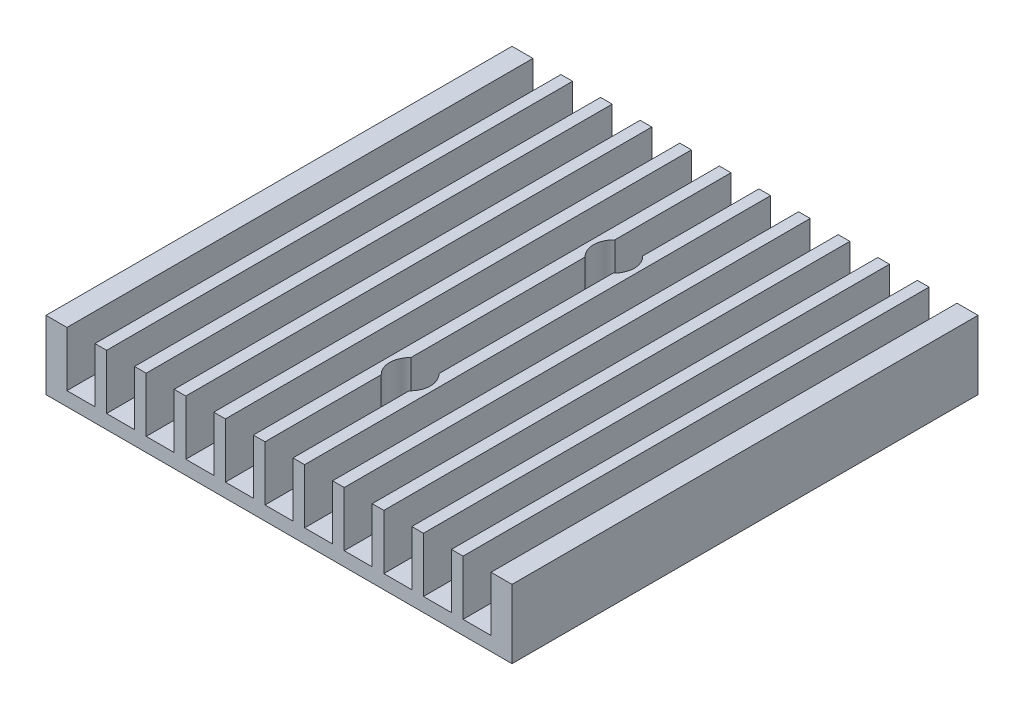
SolidWorks part; units mm, degrees
material "1060 Alloy"
ref_plane "Front Plane" through (0, 0, 0) normal (0, 0, 1) x (1, 0, 0)
ref_plane "Top Plane" through (0, 0, 0) normal (0, 1, 0) x (1, 0, 0)
ref_plane "Right Plane" through (0, 0, 0) normal (1, 0, 0) x (0, 0, -1)
sketch "Sketch1" plane through (0, 0, 0) normal (0, 1, 0) x (1, 0, 0)
  line L1 (-50.8, -50.8) -> (50.8, -50.8)
  line L2 (-50.8, -50.8) -> (-50.8, 50.8)
  line L3 (-50.8, 50.8) -> (50.8, 50.8)
  line L4 (50.8, -50.8) -> (50.8, 50.8)
  line L5 (-50.8, -50.8) -> (50.8, 50.8) construction
  line L6 (-50.8, 50.8) -> (50.8, -50.8) construction
  point P0 (0, 0)
  dimension "D1" = 101.6
  dimension "D2" = 101.6
extrude "Boss-Extrude1" add sketch "Sketch1" along normal blind 14.986 contours L1 L4 L3 L2
sketch "Sketch2" plane through (0, 0, 50.8) normal (0, 0, 1) x (1, 0, 0)
  line L0 (-50.8, 14.986) -> (50.8, 14.986) construction
  line L7 (-50.8, 0) -> (50.8, 0) construction
  line L8 (3.048, 3.048) -> (-3.048, 3.048)
  line L9 (3.048, 3.048) -> (3.048, 14.986)
  line L10 (3.048, 14.986) -> (-3.048, 14.986)
  line L11 (-3.048, 3.048) -> (-3.048, 14.986)
  line L12 (11.684, 3.048) -> (5.588, 3.048)
  line L13 (5.588, 3.048) -> (5.588, 14.986)
  line L14 (11.684, 3.048) -> (11.684, 14.986)
  line L15 (11.684, 14.986) -> (5.588, 14.986)
  line L16 (20.32, 3.048) -> (14.224, 3.048)
  line L17 (14.224, 3.048) -> (14.224, 14.986)
  line L18 (20.32, 3.048) -> (20.32, 14.986)
  line L19 (20.32, 14.986) -> (14.224, 14.986)
  line L20 (28.956, 3.048) -> (22.86, 3.048)
  line L21 (22.86, 3.048) -> (22.86, 14.986)
  line L22 (28.956, 3.048) -> (28.956, 14.986)
  line L23 (28.956, 14.986) -> (22.86, 14.986)
  line L24 (37.592, 3.048) -> (31.496, 3.048)
  line L25 (31.496, 3.048) -> (31.496, 14.986)
  line L26 (37.592, 3.048) -> (37.592, 14.986)
  line L27 (37.592, 14.986) -> (31.496, 14.986)
  line L28 (46.228, 3.048) -> (40.132, 3.048)
  line L29 (40.132, 3.048) -> (40.132, 14.986)
  line L30 (46.228, 3.048) -> (46.228, 14.986)
  line L31 (46.228, 14.986) -> (40.132, 14.986)
  line L32 (3.048, 3.048) -> (-3.048, 3.048)
  line L33 (-3.048, 3.048) -> (-3.048, 14.986)
  line L34 (3.048, 3.048) -> (3.048, 14.986)
  line L35 (3.048, 14.986) -> (-3.048, 14.986)
  line L36 (11.684, 3.048) -> (5.588, 3.048)
  line L37 (5.588, 3.048) -> (5.588, 14.986)
  line L38 (11.684, 3.048) -> (11.684, 14.986)
  line L39 (11.684, 14.986) -> (5.588, 14.986)
  line L40 (20.32, 3.048) -> (14.224, 3.048)
  line L41 (14.224, 3.048) -> (14.224, 14.986)
  line L42 (20.32, 3.048) -> (20.32, 14.986)
  line L43 (20.32, 14.986) -> (14.224, 14.986)
  line L44 (28.956, 3.048) -> (22.86, 3.048)
  line L45 (22.86, 3.048) -> (22.86, 14.986)
  line L46 (28.956, 3.048) -> (28.956, 14.986)
  line L47 (28.956, 14.986) -> (22.86, 14.986)
  line L48 (37.592, 3.048) -> (31.496, 3.048)
  line L49 (31.496, 3.048) -> (31.496, 14.986)
  line L50 (37.592, 3.048) -> (37.592, 14.986)
  line L51 (37.592, 14.986) -> (31.496, 14.986)
  line L52 (-5.588, 3.048) -> (-11.684, 3.048)
  line L53 (-11.684, 3.048) -> (-11.684, 14.986)
  line L54 (-5.588, 3.048) -> (-5.588, 14.986)
  line L55 (-5.588, 14.986) -> (-11.684, 14.986)
  line L56 (3.048, 3.048) -> (-3.048, 3.048)
  line L57 (-3.048, 3.048) -> (-3.048, 14.986)
  line L58 (3.048, 3.048) -> (3.048, 14.986)
  line L59 (3.048, 14.986) -> (-3.048, 14.986)
  line L60 (11.684, 3.048) -> (5.588, 3.048)
  line L61 (5.588, 3.048) -> (5.588, 14.986)
  line L62 (11.684, 3.048) -> (11.684, 14.986)
  line L63 (11.684, 14.986) -> (5.588, 14.986)
  line L64 (20.32, 3.048) -> (14.224, 3.048)
  line L65 (14.224, 3.048) -> (14.224, 14.986)
  line L66 (20.32, 3.048) -> (20.32, 14.986)
  line L67 (20.32, 14.986) -> (14.224, 14.986)
  line L68 (28.956, 3.048) -> (22.86, 3.048)
  line L69 (22.86, 3.048) -> (22.86, 14.986)
  line L70 (28.956, 3.048) -> (28.956, 14.986)
  line L71 (28.956, 14.986) -> (22.86, 14.986)
  line L72 (-14.224, 3.048) -> (-20.32, 3.048)
  line L73 (-20.32, 3.048) -> (-20.32, 14.986)
  line L74 (-14.224, 3.048) -> (-14.224, 14.986)
  line L75 (-14.224, 14.986) -> (-20.32, 14.986)
  line L76 (-5.588, 3.048) -> (-11.684, 3.048)
  line L77 (-11.684, 3.048) -> (-11.684, 14.986)
  line L78 (-5.588, 3.048) -> (-5.588, 14.986)
  line L79 (-5.588, 14.986) -> (-11.684, 14.986)
  line L80 (3.048, 3.048) -> (-3.048, 3.048)
  line L81 (-3.048, 3.048) -> (-3.048, 14.986)
  line L82 (3.048, 3.048) -> (3.048, 14.986)
  line L83 (3.048, 14.986) -> (-3.048, 14.986)
  line L84 (11.684, 3.048) -> (5.588, 3.048)
  line L85 (5.588, 3.048) -> (5.588, 14.986)
  line L86 (11.684, 3.048) -> (11.684, 14.986)
  line L87 (11.684, 14.986) -> (5.588, 14.986)
  line L88 (20.32, 3.048) -> (14.224, 3.048)
  line L89 (14.224, 3.048) -> (14.224, 14.986)
  line L90 (20.32, 3.048) -> (20.32, 14.986)
  line L91 (20.32, 14.986) -> (14.224, 14.986)
  line L92 (-22.86, 3.048) -> (-28.956, 3.048)
  line L93 (-28.956, 3.048) -> (-28.956, 14.986)
  line L94 (-22.86, 3.048) -> (-22.86, 14.986)
  line L95 (-22.86, 14.986) -> (-28.956, 14.986)
  line L96 (-14.224, 3.048) -> (-20.32, 3.048)
  line L97 (-20.32, 3.048) -> (-20.32, 14.986)
  line L98 (-14.224, 3.048) -> (-14.224, 14.986)
  line L99 (-14.224, 14.986) -> (-20.32, 14.986)
  line L100 (-5.588, 3.048) -> (-11.684, 3.048)
  line L101 (-11.684, 3.048) -> (-11.684, 14.986)
  line L102 (-5.588, 3.048) -> (-5.588, 14.986)
  line L103 (-5.588, 14.986) -> (-11.684, 14.986)
  line L104 (3.048, 3.048) -> (-3.048, 3.048)
  line L105 (-3.048, 3.048) -> (-3.048, 14.986)
  line L106 (3.048, 3.048) -> (3.048, 14.986)
  line L107 (3.048, 14.986) -> (-3.048, 14.986)
  line L108 (11.684, 3.048) -> (5.588, 3.048)
  line L109 (5.588, 3.048) -> (5.588, 14.986)
  line L110 (11.684, 3.048) -> (11.684, 14.986)
  line L111 (11.684, 14.986) -> (5.588, 14.986)
  line L112 (-31.496, 3.048) -> (-37.592, 3.048)
  line L113 (-37.592, 3.048) -> (-37.592, 14.986)
  line L114 (-31.496, 3.048) -> (-31.496, 14.986)
  line L115 (-31.496, 14.986) -> (-37.592, 14.986)
  line L116 (-22.86, 3.048) -> (-28.956, 3.048)
  line L117 (-28.956, 3.048) -> (-28.956, 14.986)
  line L118 (-22.86, 3.048) -> (-22.86, 14.986)
  line L119 (-22.86, 14.986) -> (-28.956, 14.986)
  line L120 (-14.224, 3.048) -> (-20.32, 3.048)
  line L121 (-20.32, 3.048) -> (-20.32, 14.986)
  line L122 (-14.224, 3.048) -> (-14.224, 14.986)
  line L123 (-14.224, 14.986) -> (-20.32, 14.986)
  line L124 (-5.588, 3.048) -> (-11.684, 3.048)
  line L125 (-11.684, 3.048) -> (-11.684, 14.986)
  line L126 (-5.588, 3.048) -> (-5.588, 14.986)
  line L127 (-5.588, 14.986) -> (-11.684, 14.986)
  line L128 (3.048, 3.048) -> (-3.048, 3.048)
  line L129 (-3.048, 3.048) -> (-3.048, 14.986)
  line L130 (3.048, 3.048) -> (3.048, 14.986)
  line L131 (3.048, 14.986) -> (-3.048, 14.986)
  line L132 (-5.588, 3.048) -> (-11.684, 3.048)
  line L133 (-11.684, 3.048) -> (-11.684, 14.986)
  line L134 (-5.588, 3.048) -> (-5.588, 14.986)
  line L135 (-5.588, 14.986) -> (-11.684, 14.986)
  line L136 (-14.224, 3.048) -> (-20.32, 3.048)
  line L137 (-20.32, 3.048) -> (-20.32, 14.986)
  line L138 (-14.224, 3.048) -> (-14.224, 14.986)
  line L139 (-14.224, 14.986) -> (-20.32, 14.986)
  line L140 (-22.86, 3.048) -> (-28.956, 3.048)
  line L141 (-28.956, 3.048) -> (-28.956, 14.986)
  line L142 (-22.86, 3.048) -> (-22.86, 14.986)
  line L143 (-22.86, 14.986) -> (-28.956, 14.986)
  line L144 (-31.496, 3.048) -> (-37.592, 3.048)
  line L145 (-37.592, 3.048) -> (-37.592, 14.986)
  line L146 (-31.496, 3.048) -> (-31.496, 14.986)
  line L147 (-31.496, 14.986) -> (-37.592, 14.986)
  line L148 (-40.132, 3.048) -> (-46.228, 3.048)
  line L149 (-46.228, 3.048) -> (-46.228, 14.986)
  line L150 (-40.132, 3.048) -> (-40.132, 14.986)
  line L151 (-40.132, 14.986) -> (-46.228, 14.986)
  point P2 (0, 3.048)
  line M9 (50.8, 14.986) -> (-50.8, 14.986)
  dimension "D1" = 3.048
  dimension "D2" = 6.096
  dimension "D3" = 6
  dimension "D4" = 6
extrude "Cut-Extrude1" cut sketch "Sketch2" against normal through all contours L28 L30 L29 M9 | L24 L26 L25 M9 | L20 L22 L21 M9 | L16 L18 L17 M9 | L12 L14 L13 M9 | L11 L8 L9 M9 | L52 L54 L53 M9 | L72 L74 L73 M9 | L92 L94 L93 M9 | L112 L114 L113 M9 | L148 L150 L149 M9 region at (-43.18, 9.017, 50.8) region at (-34.544, 9.017, 50.8) region at (-25.908, 9.017, 50.8) region at (-17.272, 9.017, 50.8) region at (-8.636, 9.017, 50.8) region at (43.18, 9.017, 50.8) region at (34.544, 9.017, 50.8) region at (25.908, 9.017, 50.8) region at (17.272, 9.017, 50.8) region at (8.636, 9.017, 50.8) region at (0, 9.017, 50.8)
sketch "Sketch3" plane through (0, 0, 0) normal (0, -1, 0) x (1, 0, 0)
  circle A0 centre (0, -22.225) radius 1.651
  circle A1 centre (0, 22.225) radius 1.651
  circle A2 centre (0, 22.225) radius 4.445
  circle A3 centre (0, -22.225) radius 4.445
  dimension "D1" = 3.302
  dimension "D4" = 8.89
  dimension "D5" = 8.89
  dimension "D2" = 22.225
  dimension "D3" = 22.225
extrude "Cut-Extrude2" cut sketch "Sketch3" against normal through all contours A1 | A0 region at (0, 0, -22.225) region at (0, 0, 22.225)
extrude "Cut-Extrude3" cut sketch "Sketch3<3>" against normal through all from surface contours A2 A1 | A3 A0 region at (-4.3193, 0, 22.225) region at (-4.3193, 0, -22.225) starting at face at (0, 3.048, 23.876)
sketch "Sketch3<3>" plane through (0, 0, 0) normal (0, -1, 0) x (1, 0, 0) same geometry as "Sketch3"
